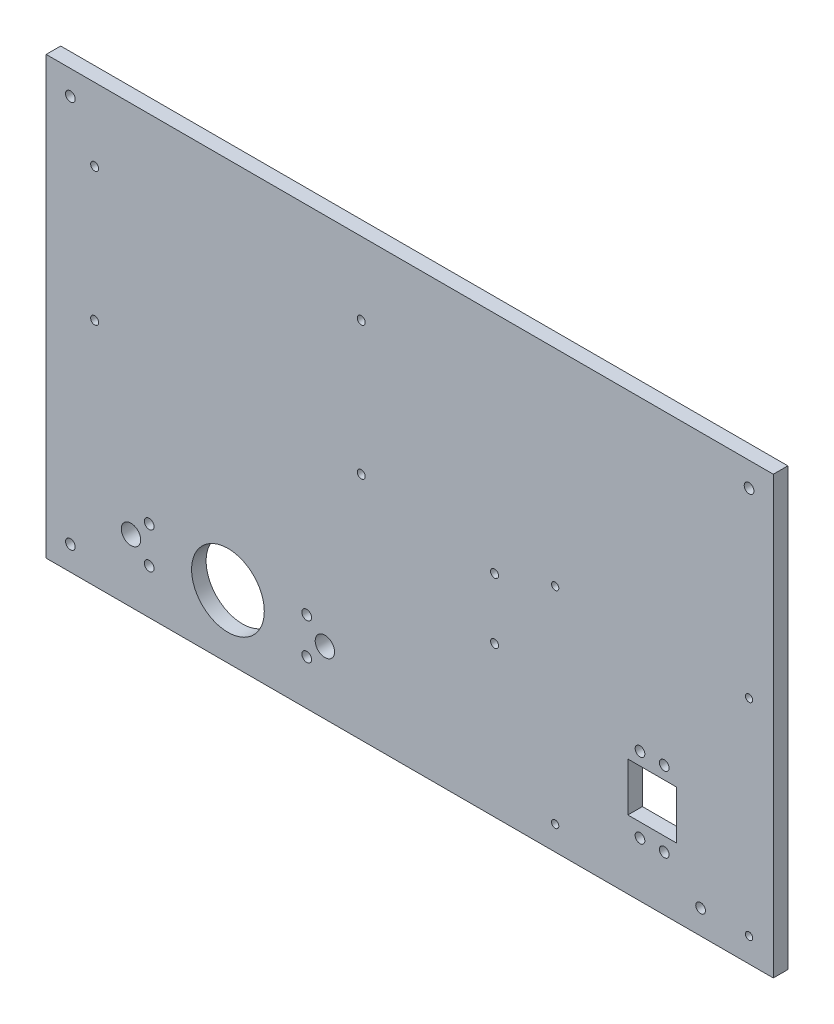
SolidWorks part; units mm, degrees
material "Faia"
ref_plane "Plano frontal" through (0, 0, 0) normal (0, 0, 1) x (1, 0, 0)
ref_plane "Plano superior" through (0, 0, 0) normal (0, 1, 0) x (1, 0, 0)
ref_plane "Plano direito" through (0, 0, 0) normal (1, 0, 0) x (0, 0, -1)
sketch "Esboço1" plane through (0, 0, 0) normal (0, 0, 1) x (1, 0, 0)
  line L0 (150, 0) -> (-150, 0) construction
  line L1 (-150, 90) -> (150, 90)
  line L2 (-150, 90) -> (-150, -90)
  line L3 (-150, -90) -> (150, -90)
  line L4 (150, 90) -> (150, -90)
  line L5 (-150, 90) -> (150, -90) construction
  line L6 (-150, -90) -> (150, 90) construction
  line L7 (70, 0) -> (-230, 0) construction
  line L8 (-83.2276, -64) -> (-64.3617, -64) construction
  line L9 (60, 5) -> (60, -80) construction
  line L10 (140, 5) -> (60, 5) construction
  line L11 (60, -80) -> (140, -80) construction
  line L12 (-75, -58.1086) -> (-75, -85.356) construction
  line L13 (90, -41.75) -> (110, -41.75)
  line L14 (90, -41.75) -> (90, -61.75)
  line L15 (90, -61.75) -> (110, -61.75)
  line L16 (110, -41.75) -> (110, -61.75)
  line L17 (90, -41.75) -> (110, -61.75) construction
  line L18 (90, -61.75) -> (110, -41.75) construction
  line L20 (-20, 5) -> (-130, 5) construction
  line L21 (-20, 5) -> (-20, 60) construction
  line L22 (-20, 60) -> (-130, 60) construction
  line L23 (-130, 5) -> (-130, 60) construction
  line L24 (-20, 5) -> (-130, 60) construction
  line L25 (-20, 60) -> (-130, 5) construction
  circle A0 centre (140, 5) radius 1.5
  circle A1 centre (140, -80) radius 1.5
  circle A2 centre (60, -80) radius 1.5
  circle A3 centre (60, 5) radius 1.5
  circle A4 centre (-107.5, -56.5) radius 2
  circle A5 centre (-42.5, -56.5) radius 2
  circle A6 centre (-75, -64) radius 15
  circle A7 centre (-35, -64) radius 4
  circle A8 centre (-115, -64) radius 4
  circle A9 centre (-42.5, -71.5) radius 2
  circle A10 centre (-107.5, -71.5) radius 2
  circle A11 centre (35, -3) radius 1.65
  circle A12 centre (35, -28) radius 1.65
  circle A13 centre (-130, 60) radius 1.65
  circle A14 centre (-20, 60) radius 1.65
  circle A15 centre (-20, 5) radius 1.65
  circle A16 centre (-130, 5) radius 1.65
  point P0 (0, 0)
  point P21 (5, 0)
  point P23 (100, -51.75)
  point P28 (100, -80)
  point P48 (-75, 32.5)
  dimension "D5" = 3
  dimension "D8" = 32.5
  dimension "D16" = 30
  dimension "D19" = 8
  dimension "D20" = 80
  dimension "D10" = 4
  dimension "D21" = 3.3
  dimension "D26" = 3.3
  dimension "D1" = 300
  dimension "D2" = 180
  dimension "D3" = 10
  dimension "D4" = 85
  dimension "D7" = 80
  dimension "D9" = 15
  dimension "D11" = 25
  dimension "D12" = 10
  dimension "D13" = 20
  dimension "D14" = 20
  dimension "D15" = 28.25
  dimension "D17" = 75
  dimension "D18" = 26
  dimension "D22" = 25
  dimension "D23" = 8
  dimension "D24" = 55
  dimension "D25" = 110
  dimension "D27" = 30
  dimension "D28" = 20
  dimension "D6" = 2
extrude "Ressalto-extrusão1" add sketch "Esboço1" along normal blind 6 contours L4 L1 L2 L3 A3 A1 A0 A2 region at (0.4455, 1.4394, 0)
sketch "Esboço2" plane through (0, 0, 6) normal (0, 0, 1) x (1, 0, 0)
  line L0 (150, 0) -> (-150, 0) construction
  line L1 (-150, 90) -> (150, 90)
  line L2 (-150, 90) -> (-150, -90)
  line L3 (-150, -90) -> (150, -90)
  line L4 (150, 90) -> (150, -90)
  line L5 (-150, 90) -> (150, -90) construction
  line L6 (-150, -90) -> (150, 90) construction
  line L7 (140, 80) -> (140, 90) construction
  line L8 (120, -80) -> (120, -90) construction
  circle A0 centre (120, -80) radius 2
  circle A1 centre (140, 80) radius 2
  circle A2 centre (-140, 80) radius 2
  circle A3 centre (-140, -80) radius 2
  point P0 (0, 0)
  point P16 (0.5357, 0)
  dimension "D3" = 4
  dimension "D1" = 300
  dimension "D2" = 180
  dimension "D4" = 10
  dimension "D5" = 30
  dimension "D6" = 10
  dimension "D7" = 10
extrude "Corte-extrusão1" cut sketch "Esboço2" against normal blind 10 contours A2 | A1 | A0 | A3 region at (120, -80, 6) region at (140, 80, 6) region at (-140, 80, 6) region at (-140, -80, 6)
sketch "Esboço3" plane through (0, 0, 6) normal (0, 0, 1) x (1, 0, 0)
  line L0 (150, 90) -> (150, -90) construction
  line L1 (-150, -90) -> (150, -90) construction
  circle A0 centre (105, -67.5) radius 2
  circle A1 centre (105, -36.5) radius 2
  circle A2 centre (95, -36.5) radius 2
  circle A3 centre (95, -67.5) radius 2
  dimension "D2" = 4
  dimension "D1" = 45
  dimension "D3" = 22.5
  dimension "D4" = 31
  dimension "D5" = 10
extrude "Corte-extrusão2" cut sketch "Esboço3" against normal blind 10
